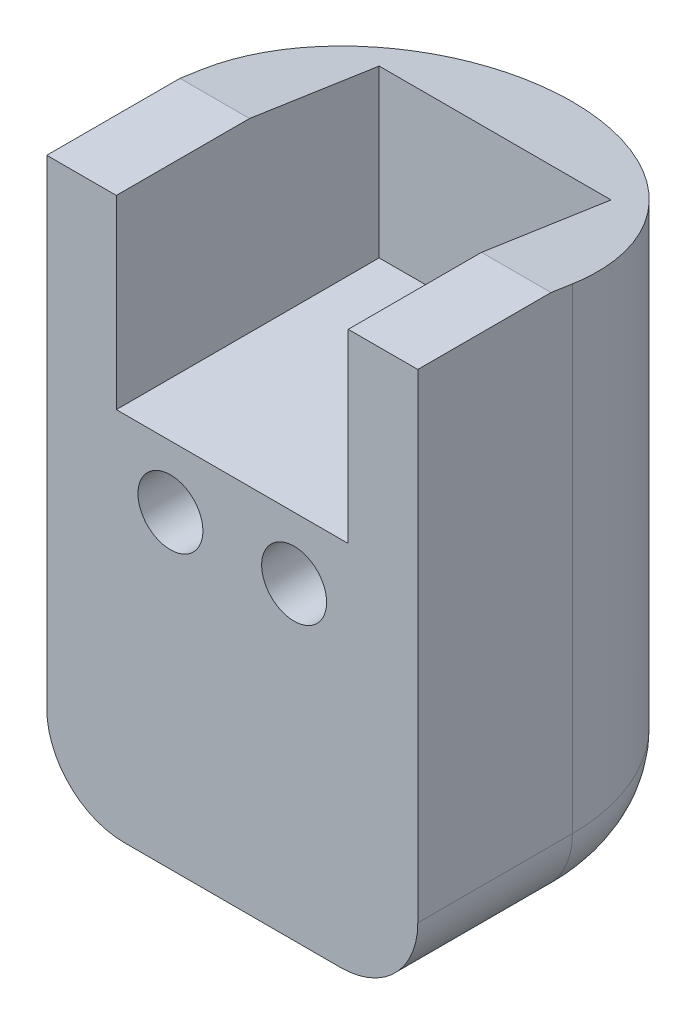
SolidWorks part; units mm, degrees
ref_plane "前视基准面" through (0, 0, 0) normal (0, 0, 1) x (1, 0, 0)
ref_plane "上视基准面" through (0, 0, 0) normal (0, 1, 0) x (1, 0, 0)
ref_plane "右视基准面" through (0, 0, 0) normal (1, 0, 0) x (0, 0, -1)
sketch "草图1" plane through (0, 0, 0) normal (0, 0, 1) x (1, 0, 0)
  line L0 (0, 0) -> (0, -36) construction
  line L1 (-7.5, 0) -> (-12, 0)
  line L2 (-12, 0) -> (-12, -36)
  line L3 (-12, -36) -> (12, -36)
  line L4 (12, -36) -> (12, 0)
  line L5 (12, 0) -> (7.5, 0)
  line L6 (-7.5, 0) -> (-7.5, -11)
  line L7 (-7.5, -11) -> (7.5, -11)
  line L8 (7.5, -11) -> (7.5, 0)
  line L9 (-7.5, 0) -> (0, 0) construction
  line L10 (0, 0) -> (7.5, 0) construction
  dimension "D1" = 12
  dimension "D2" = 36
  dimension "D3" = 11
  dimension "D4" = 15
  dimension "D5" = 7.5
extrude "凸台-拉伸1" add sketch "草图1" along normal blind 10
sketch "草图2" plane through (0, 0, 0) normal (0, 0, -1) x (-1, 0, 0)
  line L0 (-12, -36) -> (-12, 0) construction
  line L1 (-12, -11) -> (12, -11)
  line L2 (-12, -11) -> (-12, -36)
  line L3 (-12, -36) -> (12, -36)
  line L4 (12, -11) -> (12, -36)
  dimension "D1" = 25
extrude "凸台-拉伸2" add sketch "草图2" along normal blind 12
sketch "草图3" plane through (0, -11, 0) normal (0, 1, 0) x (1, 0, 0)
  line L0 (-7.5, 0) -> (-7.5, 7)
  line L1 (-7.5, 7) -> (7.5, 7)
  line L2 (7.5, 7) -> (7.5, 0)
  line L3 (7.5, 0) -> (12, 0)
  line L4 (12, 0) -> (12, 12)
  line L5 (12, 12) -> (-12, 12)
  line L6 (-12, 12) -> (-12, 0)
  line L7 (-12, 0) -> (-7.5, 0)
  dimension "D1" = 7
extrude "凸台-拉伸3" add sketch "草图3" along normal up to surface (11 mm away) up to face at (9.75, 0, 5)
sketch "草图4" plane through (0, 0, 0) normal (1, 0, 0) x (0, 0, -1)
  line L0 (-1.3823, 0) -> (12, -2)
  line L1 (-10, 0) -> (12, 0) construction
  line L2 (12, 0) -> (12, -36) construction
  line L3 (12, -2) -> (12, 0)
  line L4 (12, 0) -> (-1.3823, 0)
  dimension "D1" = 2
  dimension "D2" = 8.5
extrude "切除-拉伸1" cut sketch "草图4" against normal mid plane 30
sketch "草图5" plane through (0, -11, 0) normal (0, 1, 0) x (1, 0, 0)
  line L4 (7.5, -10) -> (7.5, 7)
  line L5 (7.5, 7) -> (-7.5, 7)
  line L6 (-7.5, 7) -> (-7.5, -10)
  line L7 (-7.5, -10) -> (7.5, -10)
  line L8 (7.5, -10) -> (7.5, 7)
  line L9 (7.5, 7) -> (-7.5, 7)
  line L10 (-7.5, 7) -> (-7.5, -10)
  line L11 (-7.5, -10) -> (7.5, -10)
  dimension "D1" = 0
extrude "切除-拉伸2" cut sketch "草图5" against normal blind 1
fillet "圆角2" radius 12 2 edges at (12, -19, -12) (-12, -19, -12)
fillet "圆角3" radius 5 4 edges at (-12, -36, 5) (-8.4853, -36, -8.4853) (8.4853, -36, -8.4853) (12, -36, 5)
sketch "草图6" plane through (0, 0, 10) normal (0, 0, 1) x (1, 0, 0)
  line L0 (0, -36) -> (0, -16) construction
  line L1 (-7, -36) -> (7, -36) construction
  line L2 (0, -16) -> (4, -16) construction
  circle A0 centre (4, -16) radius 2.1
  circle A1 centre (-4, -16) radius 2.1
  dimension "D1" = 4.2
  dimension "D2" = 4
  dimension "D3" = 20
extrude "切除-拉伸3" cut sketch "草图6" against normal blind 30
sketch "草图7" plane through (0, 0, 10) normal (0, 0, 1) x (1, 0, 0)
  circle A0 centre (4, -16) radius 3.5
  circle A1 centre (-4, -16) radius 3.5
  dimension "D1" = 7
  dimension "D2" = 7
extrude "切除-拉伸4" cut sketch "草图7" against normal blind 10 from offset 15 offset against normal yes
